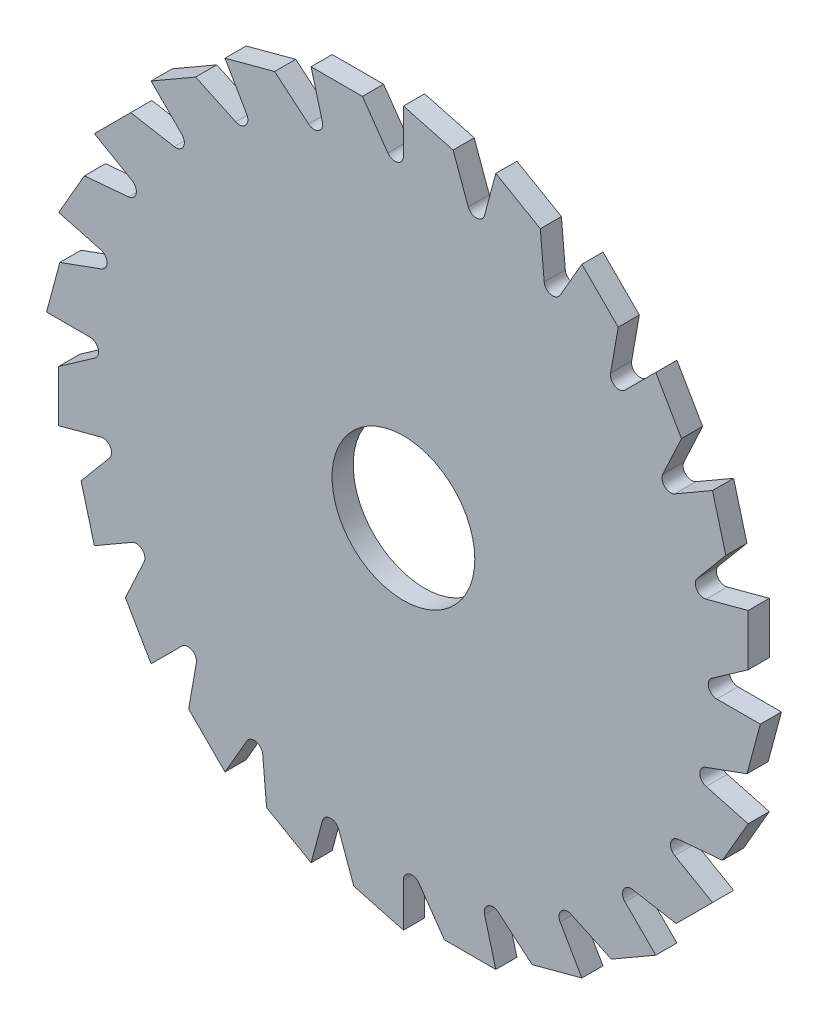
SolidWorks part; units mm, degrees
ref_plane "Front Plane" through (0, 0, 0) normal (0, 0, 1) x (1, 0, 0)
ref_plane "Top Plane" through (0, 0, 0) normal (0, 1, 0) x (1, 0, 0)
ref_plane "Right Plane" through (0, 0, 0) normal (1, 0, 0) x (0, 0, -1)
sketch "Sketch1" plane through (0, 0, 0) normal (0, 0, 1) x (1, 0, 0)
  line L0 (0, 31.75) -> (4.4162, 30.5667)
  line L1 (4.4162, 30.5667) -> (5.7634, 26.8652)
  line L2 (7.2155, 26.9286) -> (8.2175, 30.6681)
  line L3 (0, 31.75) -> (0, 0) construction
  line L4 (0, 0) -> (8.2175, 30.6681) construction
  line L5 (0, 31.75) -> (12.0811, 31.75) construction
  line L6 (6.3024, 26.3847) -> (0, 0) construction
  line L7 (6.3024, 26.3847) -> (4.0698, 26.918) construction
  line L8 (13.9393, 24.1436) -> (15.875, 27.4963)
  line L9 (12.177, 28.3821) -> (12.5203, 24.4581)
  line L10 (8.2175, 30.6681) -> (12.177, 28.3821)
  line L11 (19.7131, 19.7131) -> (22.4506, 22.4506)
  line L12 (19.1079, 24.2634) -> (18.4239, 20.3843)
  line L13 (15.875, 27.4963) -> (19.1079, 24.2634)
  line L14 (24.1436, 13.9393) -> (27.4963, 15.875)
  line L15 (24.7366, 18.4912) -> (23.072, 14.9212)
  line L16 (22.4506, 22.4506) -> (24.7366, 18.4912)
  line L17 (26.9286, 7.2155) -> (30.6681, 8.2175)
  line L18 (28.6796, 11.4588) -> (26.1477, 8.4413)
  line L19 (27.4963, 15.875) -> (28.6796, 11.4588)
  line L20 (27.8786, 0) -> (31.75, 0)
  line L21 (30.6681, 3.6455) -> (27.4415, 1.3862)
  line L22 (30.6681, 8.2175) -> (30.6681, 3.6455)
  line L23 (26.9286, -7.2155) -> (30.6681, -8.2175)
  line L24 (30.5667, -4.4162) -> (26.8652, -5.7634)
  line L25 (31.75, 0) -> (30.5667, -4.4162)
  line L26 (24.1436, -13.9393) -> (27.4963, -15.875)
  line L27 (28.3821, -12.177) -> (24.4581, -12.5203)
  line L28 (30.6681, -8.2175) -> (28.3821, -12.177)
  line L29 (19.7131, -19.7131) -> (22.4506, -22.4506)
  line L30 (24.2634, -19.1079) -> (20.3843, -18.4239)
  line L31 (27.4963, -15.875) -> (24.2634, -19.1079)
  line L32 (13.9393, -24.1436) -> (15.875, -27.4963)
  line L33 (18.4912, -24.7366) -> (14.9212, -23.072)
  line L34 (22.4506, -22.4506) -> (18.4912, -24.7366)
  line L35 (7.2155, -26.9286) -> (8.2175, -30.6681)
  line L36 (11.4588, -28.6796) -> (8.4413, -26.1477)
  line L37 (15.875, -27.4963) -> (11.4588, -28.6796)
  line L38 (0, -27.8786) -> (0, -31.75)
  line L39 (3.6455, -30.6681) -> (1.3862, -27.4415)
  line L40 (8.2175, -30.6681) -> (3.6455, -30.6681)
  line L41 (-7.2155, -26.9286) -> (-8.2175, -30.6681)
  line L42 (-4.4162, -30.5667) -> (-5.7634, -26.8652)
  line L43 (0, -31.75) -> (-4.4162, -30.5667)
  line L44 (-13.9393, -24.1436) -> (-15.875, -27.4963)
  line L45 (-12.177, -28.3821) -> (-12.5203, -24.4581)
  line L46 (-8.2175, -30.6681) -> (-12.177, -28.3821)
  line L47 (-19.7131, -19.7131) -> (-22.4506, -22.4506)
  line L48 (-19.1079, -24.2634) -> (-18.4239, -20.3843)
  line L49 (-15.875, -27.4963) -> (-19.1079, -24.2634)
  line L50 (-24.1436, -13.9393) -> (-27.4963, -15.875)
  line L51 (-24.7366, -18.4912) -> (-23.072, -14.9212)
  line L52 (-22.4506, -22.4506) -> (-24.7366, -18.4912)
  line L53 (-26.9286, -7.2155) -> (-30.6681, -8.2175)
  line L54 (-28.6796, -11.4588) -> (-26.1477, -8.4413)
  line L55 (-27.4963, -15.875) -> (-28.6796, -11.4588)
  line L56 (-27.8786, 0) -> (-31.75, 0)
  line L57 (-30.6681, -3.6455) -> (-27.4415, -1.3862)
  line L58 (-30.6681, -8.2175) -> (-30.6681, -3.6455)
  line L59 (-26.9286, 7.2155) -> (-30.6681, 8.2175)
  line L60 (-30.5667, 4.4162) -> (-26.8652, 5.7634)
  line L61 (-31.75, 0) -> (-30.5667, 4.4162)
  line L62 (-24.1436, 13.9393) -> (-27.4963, 15.875)
  line L63 (-28.3821, 12.177) -> (-24.4581, 12.5203)
  line L64 (-30.6681, 8.2175) -> (-28.3821, 12.177)
  line L65 (-19.7131, 19.7131) -> (-22.4506, 22.4506)
  line L66 (-24.2634, 19.1079) -> (-20.3843, 18.4239)
  line L67 (-27.4963, 15.875) -> (-24.2634, 19.1079)
  line L68 (-13.9393, 24.1436) -> (-15.875, 27.4963)
  line L69 (-18.4912, 24.7366) -> (-14.9212, 23.072)
  line L70 (-22.4506, 22.4506) -> (-18.4912, 24.7366)
  line L71 (-7.2155, 26.9286) -> (-8.2175, 30.6681)
  line L72 (-11.4588, 28.6796) -> (-8.4413, 26.1477)
  line L73 (-15.875, 27.4963) -> (-11.4588, 28.6796)
  line L74 (0, 27.8786) -> (0, 31.75)
  line L75 (-3.6455, 30.6681) -> (-1.3862, 27.4415)
  line L76 (-8.2175, 30.6681) -> (-3.6455, 30.6681)
  circle A0 centre (0, 0) radius 31.75 construction
  circle A1 centre (0, 0) radius 6.35
  circle A2 centre (0, 0) radius 27.127 construction
  arc A3 (5.7634, 26.8652) -> (7.2155, 26.9286) centre (6.4795, 27.1259) ccw
  arc A4 (12.5203, 24.4581) -> (13.9393, 24.1436) centre (13.2794, 24.5246) ccw
  arc A5 (18.4239, 20.3843) -> (19.7131, 19.7131) centre (19.1743, 20.2519) ccw
  arc A6 (23.072, 14.9212) -> (24.1436, 13.9393) centre (23.7626, 14.5992) ccw
  arc A7 (26.1477, 8.4413) -> (26.9286, 7.2155) centre (26.7314, 7.9515) ccw
  arc A8 (27.4415, 1.3862) -> (27.8786, 0) centre (27.8786, 0.762) ccw
  arc A9 (26.8652, -5.7634) -> (26.9286, -7.2155) centre (27.1259, -6.4795) ccw
  arc A10 (24.4581, -12.5203) -> (24.1436, -13.9393) centre (24.5246, -13.2794) ccw
  arc A11 (20.3843, -18.4239) -> (19.7131, -19.7131) centre (20.2519, -19.1743) ccw
  arc A12 (14.9212, -23.072) -> (13.9393, -24.1436) centre (14.5992, -23.7626) ccw
  arc A13 (8.4413, -26.1477) -> (7.2155, -26.9286) centre (7.9515, -26.7314) ccw
  arc A14 (1.3862, -27.4415) -> (0, -27.8786) centre (0.762, -27.8786) ccw
  arc A15 (-5.7634, -26.8652) -> (-7.2155, -26.9286) centre (-6.4795, -27.1259) ccw
  arc A16 (-12.5203, -24.4581) -> (-13.9393, -24.1436) centre (-13.2794, -24.5246) ccw
  arc A17 (-18.4239, -20.3843) -> (-19.7131, -19.7131) centre (-19.1743, -20.2519) ccw
  arc A18 (-23.072, -14.9212) -> (-24.1436, -13.9393) centre (-23.7626, -14.5992) ccw
  arc A19 (-26.1477, -8.4413) -> (-26.9286, -7.2155) centre (-26.7314, -7.9515) ccw
  arc A20 (-27.4415, -1.3862) -> (-27.8786, 0) centre (-27.8786, -0.762) ccw
  arc A21 (-26.8652, 5.7634) -> (-26.9286, 7.2155) centre (-27.1259, 6.4795) ccw
  arc A22 (-24.4581, 12.5203) -> (-24.1436, 13.9393) centre (-24.5246, 13.2794) ccw
  arc A23 (-20.3843, 18.4239) -> (-19.7131, 19.7131) centre (-20.2519, 19.1743) ccw
  arc A24 (-14.9212, 23.072) -> (-13.9393, 24.1436) centre (-14.5992, 23.7626) ccw
  arc A25 (-8.4413, 26.1477) -> (-7.2155, 26.9286) centre (-7.9515, 26.7314) ccw
  arc A26 (-1.3862, 27.4415) -> (0, 27.8786) centre (-0.762, 27.8786) ccw
  dimension "D1" = 63.5
  dimension "D2" = 12.7
  dimension "D3" = 125
  dimension "D7" = 0.762
  dimension "D4" = 15
  dimension "D5" = 15
  dimension "D6" = 4.572
  dimension "D8" = 24
extrude "Boss-Extrude1" add sketch "Sketch1" along normal blind 1.8796 contours A26 L75 L76 L71 A25 L72 L73 L68 A24 L69 L70 L65 A23 L66 L67 L62 A22 L63 L64 L59 A21 L60 L61 L56 A20 L57 L58 L53 A19 L54 L55 L50 A18 L51 L52 L47 A17 L48 L49 L44 A16 L45 L46 L41 A15 L42 L43 L38 A14 L39 L40 region at (1.9757, 30.2909, 0)
ref_plane "Plane1" through (0, 0, 0.9398) normal (0, 0, 1) x (1, 0, 0)
